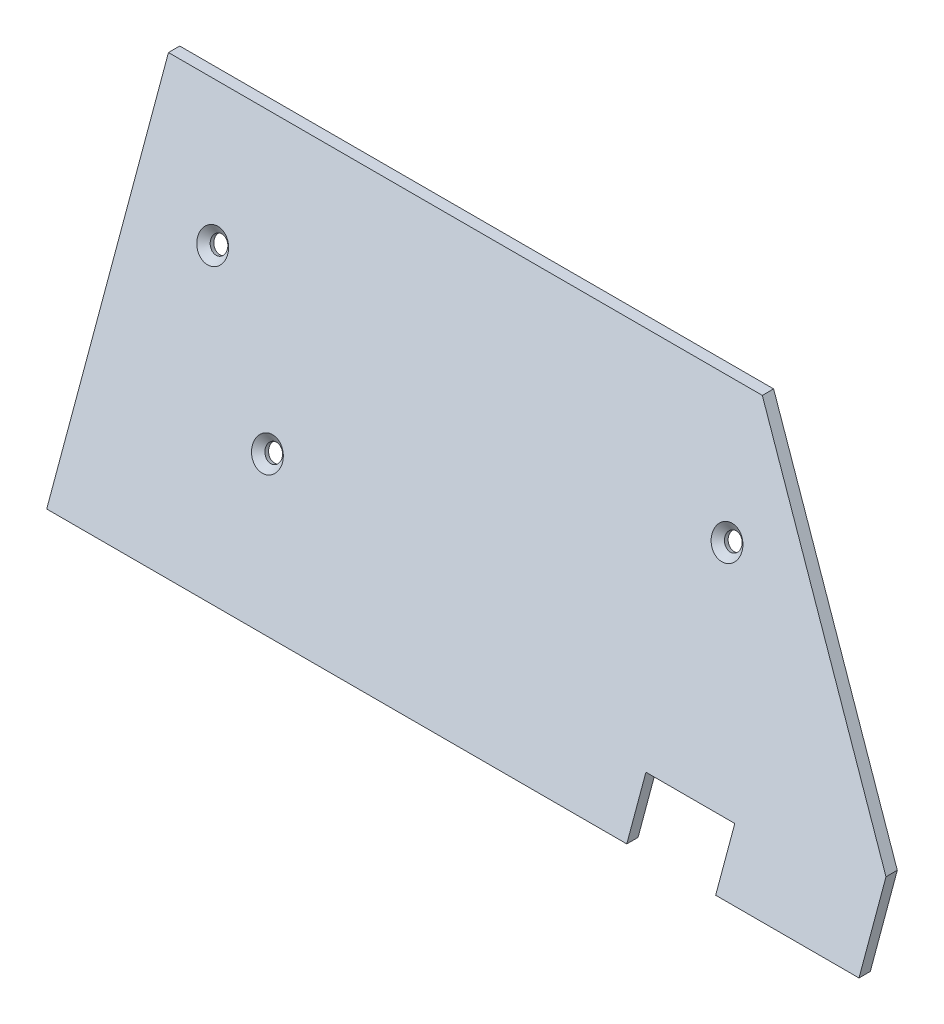
SolidWorks part; units mm, degrees
ref_plane "Front Plane" through (0, 0, 0) normal (0, 0, 1) x (1, 0, 0)
ref_plane "Top Plane" through (0, 0, 0) normal (0, 1, 0) x (1, 0, 0)
ref_plane "Right Plane" through (0, 0, 0) normal (1, 0, 0) x (0, 0, -1)
sketch "Sketch1" plane through (0, 0, 0) normal (1, 0, 0) x (0, 0, -1)
  line L0 (0, 0) -> (-2.3622, 0)
  line L1 (-2.3622, 0) -> (23.1157, 70)
  line L2 (23.1157, 70) -> (25.4779, 70)
  line L3 (25.4779, 70) -> (0, 0)
  dimension "D1" = 2.3622
  dimension "D2" = 2.3622
  dimension "D3" = 70
  dimension "D4" = 70
extrude "Main" add sketch "Sketch1" along normal mid plane 170
hole_wizard "BackBracketHoles" positions "Sketch2" profile "Sketch3" countersink size "M3" standard "ANSI Metric"
sketch "Sketch2" plane through (0, 0.7592, 2.0859) normal (0, 0.342, 0.9397) x (1, 0, 0)
  line L0 (-85, 73.6845) -> (-85, -0.8079) construction
  line L1 (85, -0.8079) -> (-85, -0.8079) construction
  point P0 (-67.6378, 50.0021)
  point P2 (-47.6378, 25.0021)
  dimension "D1" = 17.3622
  dimension "D2" = 50.81
  dimension "D3" = 25.81
  dimension "D4" = 37.3622
sketch "Sketch3" plane through (-67.6378, 47.7458, -15.0158) normal (1, 0, 0) x (0, -0.9397, 0.342)
  line L0 (0, 0) -> (0, 5)
  line L1 (0, 5) -> (1.75, 5)
  line L2 (1.75, 5) -> (1.75, 1.4)
  line L3 (1.75, 1.4) -> (3.15, 0)
  line L5 (3.15, 0) -> (0, 0)
  line L6 (-1.75, 1.4) -> (-3.15, 0) construction
  line L10 (0, 5) -> (-1.75, 5) construction
  line L11 (0, -6.35) -> (0, 107.95) construction
  dimension "Hole Dia." = 3.5
  dimension "Hole Depth" = 5
  dimension "Near C'Sink Dia." = 6.3
  dimension "Near C'Sink Angle" = 90
  dimension "Drill Angle" = 180
sketch "Sketch4" plane through (0, 0, 0) normal (0, 0, 1) x (1, 0, 0)
  line L0 (85.1927, -2.3534) -> (100, -2.3534)
  line L1 (100, -2.3534) -> (39.2883, 70)
  line L2 (85, 70) -> (-85, 70) construction
  line L3 (39.2883, 70) -> (39.2883, 0)
  line L4 (85, 0) -> (-85, 0) construction
  line L5 (39.2883, 0) -> (85.1927, -2.3534)
  line L6 (100, -2.3534) -> (100, 70)
  line L7 (100, 70) -> (39.2883, 70)
  line L8 (85, 70) -> (85, 0) construction
  dimension "D1" = 50
  dimension "D2" = 15
extrude "Cut-Extrude1" cut sketch "Sketch4" against normal blind 28.6 contours L6 L7 L1 region at (79.7628, 45.8822, 0)
hole_wizard "CSK for M3 Flat Head Machine Screw1" positions "Sketch5" profile "Sketch6" countersink size "M3" standard "ANSI Metric"
sketch "Sketch5" plane through (0, 0.7592, 2.0859) normal (0, 0.342, 0.9397) x (1, 0, 0)
  line L0 (30, 60.0021) -> (52.6886, 60.0021) construction
  line L1 (30, 60.0021) -> (30, 32.9616) construction
  point P0 (40, 50.0021)
  dimension "D1" = 10
  dimension "D2" = 10
sketch "Sketch6" plane through (40, 47.7458, -15.0158) normal (1, 0, 0) x (0, -0.9397, 0.342)
  line L0 (0, 0) -> (0, 5)
  line L1 (0, 5) -> (1.75, 5)
  line L2 (1.75, 5) -> (1.75, 1.4)
  line L3 (1.75, 1.4) -> (3.15, 0)
  line L5 (3.15, 0) -> (0, 0)
  line L6 (-1.75, 1.4) -> (-3.15, 0) construction
  line L10 (0, 5) -> (-1.75, 5) construction
  line L11 (0, -6.35) -> (0, 107.95) construction
  dimension "Hole Dia." = 3.5
  dimension "Hole Depth" = 5
  dimension "Near C'Sink Dia." = 6.3
  dimension "Near C'Sink Angle" = 90
  dimension "Drill Angle" = 180
sketch "Sketch7" plane through (0, 0, 0) normal (0, 0, 1) x (1, 0, 0)
  line L0 (36.4, 11.002) -> (36.4, 0.002) construction
  line L1 (36.4, 11.002) -> (55, 11.002)
  line L2 (36.4, 11.002) -> (36.4, 0.002)
  line L3 (36.4, 0.002) -> (55, 0.002)
  line L4 (55, 11.002) -> (55, 0.002)
  line L6 (36.4, 11.002) -> (55, 11.002) construction
  line L7 (36.4, 0.002) -> (55, 0.002)
  line L8 (36.4, 0.002) -> (36.4, -0.998)
  line L9 (36.4, -0.998) -> (55, -0.998)
  line L10 (55, 0.002) -> (55, -0.998)
  dimension "D1" = 1
extrude "Cut-Extrude3" cut sketch "Sketch7" against normal up to surface (29.6367 mm away) from offset 30 contours L10 L3 L8 L9 | L4 L1 L2 L3 region at (45.7, 5.502, 0) region at (45.7, -0.498, 0) up to face at (40, 45.3421, -16.5032)
